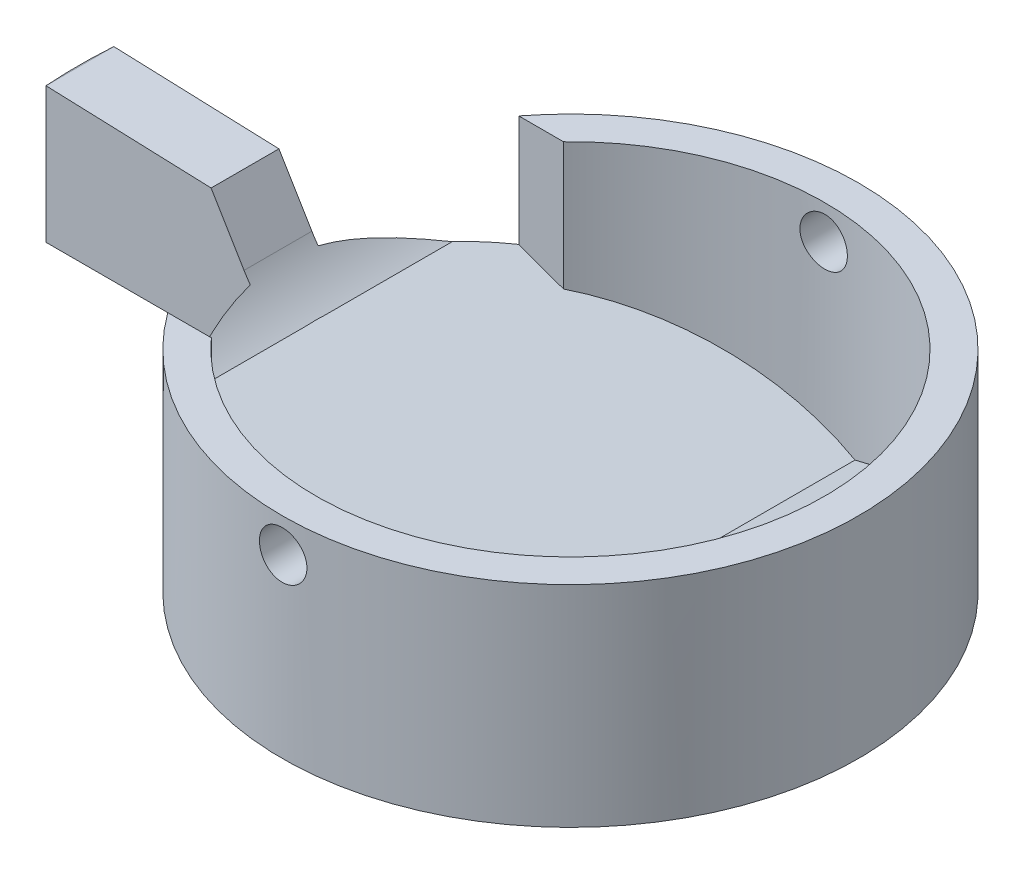
SolidWorks part; units mm, degrees
ref_plane "Front Plane" through (0, 0, 0) normal (0, 0, 1) x (1, 0, 0)
ref_plane "Top Plane" through (0, 0, 0) normal (0, 1, 0) x (1, 0, 0)
ref_plane "Right Plane" through (0, 0, 0) normal (1, 0, 0) x (0, 0, -1)
sketch "Sketch1" plane through (0, 0, 0) normal (0, 1, 0) x (1, 0, 0)
  circle A0 centre (0, 0) radius 9.525
  circle A1 centre (0, 0) radius 10.795
  dimension "D1" = 19.05
  dimension "D2" = 1.27
extrude "Boss-Extrude1" add sketch "Sketch1" along normal blind 2.54 contours A1
sketch "Sketch2" plane through (0, 2.54, 0) normal (0, 1, 0) x (1, 0, 0)
  circle A0 centre (0, 0) radius 9.525
  circle A1 centre (0, 0) radius 10.795
  circle A2 centre (0, 0) radius 10.795 construction
  dimension "D1" = 19.05
extrude "Boss-Extrude2" add sketch "Sketch2" along normal blind 12.7
ref_plane "Plane1" through (0, 12.7, 0) normal (0, 1, 0) x (1, 0, 0)
sketch "Sketch3" plane through (0, 0, 0) normal (0, 0, 1) x (1, 0, 0)
  line L1 (9.525, 2.54) -> (-9.525, 2.54) construction
  line L2 (-9.525, 11.43) -> (-9.525, 2.54)
  line L3 (-9.525, 2.54) -> (9.525, 2.54)
  line L4 (-9.525, 11.43) -> (9.525, 4.5134)
  line L5 (9.525, 4.5134) -> (9.525, 2.54)
  dimension "D1" = 8.89
  dimension "D2" = 1.9734
extrude "Boss-Extrude3" add sketch "Sketch3" along normal mid plane 19.05 contours L2 L3 L5 L4
sketch "Sketch4" plane through (0, 15.24, 0) normal (0, 1, 0) x (1, 0, 0)
  circle A0 centre (0, 0) radius 10.795
  circle A1 centre (0, 0) radius 13.4704
  circle A2 centre (0, 0) radius 10.795 construction
extrude "Cut-Extrude1" cut sketch "Sketch4" against normal up to surface (15.24 mm away) up to face at (0, 0, 10.795)
sketch "Sketch5" plane through (0, 15.24, 0) normal (0, 1, 0) x (1, 0, 0)
  line L0 (0, 0) -> (-16.3634, 0) construction
  line L2 (-9.525, 1.27) -> (-18.3712, 1.27)
  line L3 (-9.525, 1.27) -> (-9.525, -1.27)
  line L4 (-9.525, -1.27) -> (-18.3712, -1.27)
  arc A0 (-18.3712, 1.27) -> (-18.3712, -1.27) centre (0, 0) ccw
  circle A1 centre (0, 0) radius 10.795 construction
  dimension "D1" = 7.62
  dimension "D2" = 1.27
  dimension "D3" = 1.27
  dimension "D4" = 9.525
extrude "Boss-Extrude4" add sketch "Sketch5" against normal blind 5.08
sketch "Sketch7" plane through (0, 0, -1.27) normal (0, 0, -1) x (-1, 0, 0)
  line L0 (18.3712, 13.6281) -> (18.3712, 15.24)
  line L2 (18.3712, 15.24) -> (8.9498, 14.8981)
  line L6 (10.72, 15.24) -> (18.3712, 15.24) construction
  line L7 (18.3712, 10.16) -> (18.3712, 15.24) construction
  line L9 (18.3712, 15.24) -> (8.9801, 16.51)
  line L14 (8.9801, 16.51) -> (8.9498, 14.8981)
  dimension "D1" = 1.6119
  dimension "D2" = 0
  dimension "D3" = 0
  dimension "D4" = 1.6119
extrude "Cut-Extrude6" cut sketch "Sketch7" against normal blind 3.81 and the other way blind 1.27 contours L2 L14 L9
fillet "Fillet1" radius 2.54 2 edges at (-9.836, 15.24, -2.54) (-9.836, 15.24, 2.54)
ref_plane "Plane2" through (0, 0, 0) normal (0, 0, -1) x (-1, 0, 0)
ref_plane "Plane3" through (0, 0, -6.604) normal (0, 0, -1) x (-1, 0, 0)
sketch "Sketch8" plane through (0, 0, 0) normal (0, 0, 1) x (1, 0, 0)
  line L0 (-10.606, 14.9582) -> (10.795, 14.9582) construction
  line L1 (-10.4919, 14.9541) -> (-10.72, 14.9623) construction
  line L2 (10.795, 0) -> (10.795, 15.24) construction
  line L3 (0, -15.24) -> (0, 15.24) construction
  line L4 (10.795, 15.24) -> (-10.1269, 15.24) construction
  line L5 (9.525, 15.24) -> (-8.7213, 15.24) construction
  circle A0 centre (0, 13.97) radius 0.889
  point P12 (0, 0)
  dimension "D2" = 1.778
  dimension "D1" = 1.27
extrude "Cut-Extrude7" cut sketch "Sketch8" against normal through all both and the other way through all
sketch "Sketch9" plane through (0, 0, -6.604) normal (0, 0, -1) x (-1, 0, 0)
  line L1 (9.525, 11.43) -> (-9.525, 4.5134) construction
  line L2 (18.3712, 15.24) -> (10.72, 14.9623) construction
  line L3 (11.6344, 14.9955) -> (5.6712, 16.0646)
  line L4 (9.5183, 11.4276) -> (7.1376, 10.5632)
  line L5 (7.1376, 10.5632) -> (5.6712, 10.0308)
  line L6 (5.6712, 16.0646) -> (5.6712, 10.0308)
  line L7 (18.3712, 10.16) -> (18.3712, 15.24) construction
  line L8 (10.72, 10.16) -> (10.72, 14.9623) construction
  line L10 (10.9542, 12.9596) -> (12.1869, 15.0156)
  line L11 (12.1869, 15.0156) -> (5.6712, 16.0646)
  arc A0 (11.6344, 14.9955) -> (9.5183, 11.4276) centre (6.6917, 15.5155) cw
  dimension "D1" = 12.7
  dimension "D2" = 0.9144
  dimension "D3" = 0.0254
extrude "Cut-Extrude8" cut sketch "Sketch9" against normal blind 12.954 contours L3 A0 L10 L11 | L3 L6 L5 L4 A0 region at (-8.6541, 15.5372, -6.604)
sketch "Sketch10" plane through (0, 0, 0) normal (0, 0, 1) x (1, 0, 0)
  line L0 (-7.0995, 10.5494) -> (9.5248, 10.5494)
  line L3 (9.5248, 10.5494) -> (-7.0995, 4.5143)
  line L4 (9.5248, 10.5494) -> (9.5248, 4.5135)
  line L5 (9.525, 4.5134) -> (-7.0995, 10.5494) construction
  line L6 (9.5248, 4.5135) -> (-7.0995, 4.5143)
  dimension "D1" = 16.6243
  dimension "D2" = 6.035
extrude "Boss-Extrude5" add sketch "Sketch10" along normal mid plane 21.336 contours L6 L4 L3 region at (3.9834, 6.5257, 0)
sketch "Sketch11" plane through (0, 15.24, 0) normal (0, 1, 0) x (1, 0, 0)
  line L0 (-9.9486, -10.9806) -> (-10.4527, -2.6969)
  line L1 (-10.4527, 2.6969) -> (-10.0687, 10.8706)
  line L2 (-10.4527, -2.6969) -> (-10.4527, 2.6969)
  arc A0 (-10.4527, -2.6969) -> (-10.4527, 2.6969) centre (0, 0) ccw
  arc A1 (-9.9486, -10.9806) -> (-10.0687, 10.8706) centre (0, 0) ccw
  arc M9 (-8.7298, -6.35) -> (-8.5393, 6.604) centre (0, 0) ccw
extrude "Cut-Extrude9" cut sketch "Sketch11" against normal up to surface (15.24 mm away) contours L0 A1 L1 A0 M9 region at (-9.8119, 15.24, 6.8151) up to face at (0, 0, 10.795)
sketch "Sketch12" plane through (0, 0, 0) normal (0, -1, 0) x (1, 0, 0)
  circle A0 centre (0, 0) radius 10.795
  circle A1 centre (0, 0) radius 10.795 construction
extrude "Cut-Extrude10" cut sketch "Sketch12" against normal blind 7.366
equation "\"D1@Sketch9\"=\"D1@Sketch5\" + .2"
